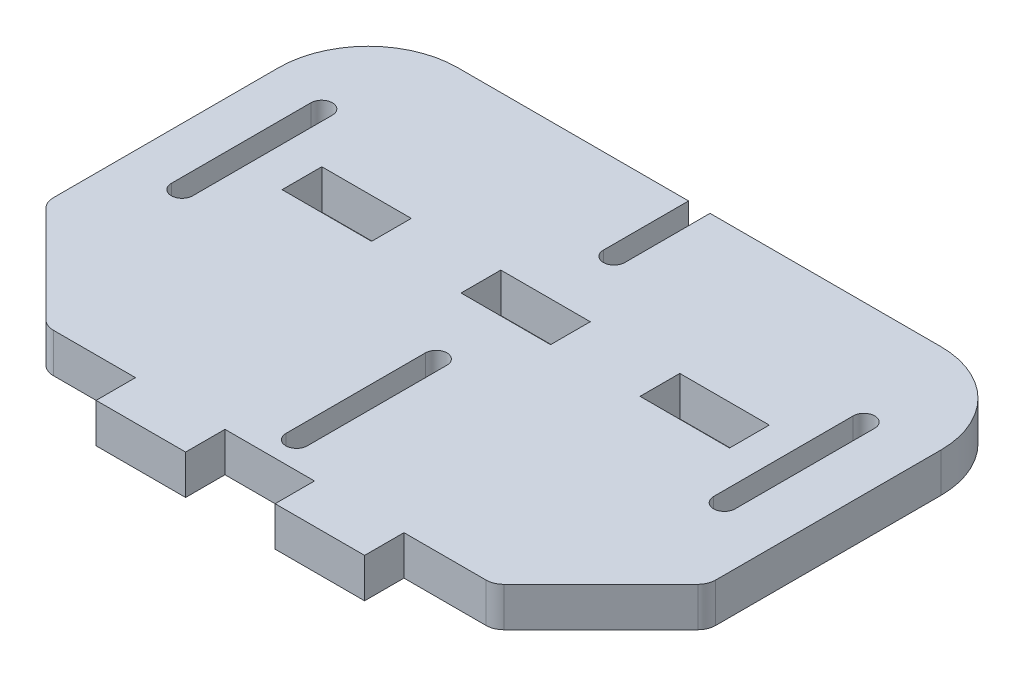
SolidWorks part; units mm, degrees
ref_plane "Front Plane" through (0, 0, 0) normal (0, 0, 1) x (1, 0, 0)
ref_plane "Top Plane" through (0, 0, 0) normal (0, 1, 0) x (1, 0, 0)
ref_plane "Right Plane" through (0, 0, 0) normal (1, 0, 0) x (0, 0, -1)
sketch "Sketch1" plane through (0, 0, 0) normal (0, 1, 0) x (1, 0, 0)
  line L8 (0, -7.5) -> (125, -7.5)
  line L12 (0, -7.5) -> (0, 3.5)
  line L14 (125, -7.5) -> (125, 3.5)
  line L17 (155, 33.5) -> (155, 123.5)
  line L18 (-30, 33.5) -> (-30, 123.5)
  line L23 (137.5, 55.5) -> (137.5, 94.5) construction
  line L24 (134.5, 55.5) -> (134.5, 94.5)
  line L25 (140.5, 55.5) -> (140.5, 94.5)
  line L26 (-14, 55.5) -> (-14, 94.5) construction
  line L27 (-17, 55.5) -> (-17, 94.5)
  line L28 (-11, 55.5) -> (-11, 94.5)
  line L29 (62.5, 11) -> (62.5, 50) construction
  line L30 (59.5, 11) -> (59.5, 50)
  line L31 (65.5, 11) -> (65.5, 50)
  line L32 (59.5, 123.5) -> (-30, 123.5)
  line L33 (65.5, 123.5) -> (65.5, 99.7057)
  line L34 (59.5, 123.5) -> (59.5, 99.7057)
  line L35 (155, 123.5) -> (65.5, 123.5)
  line L36 (125, 3.5) -> (155, 33.5)
  line L37 (0, 3.5) -> (-30, 33.5)
  arc A0 (134.5, 55.5) -> (140.5, 55.5) centre (137.5, 55.5) ccw
  arc A1 (140.5, 94.5) -> (134.5, 94.5) centre (137.5, 94.5) ccw
  arc A2 (-17, 55.5) -> (-11, 55.5) centre (-14, 55.5) ccw
  arc A3 (-11, 94.5) -> (-17, 94.5) centre (-14, 94.5) ccw
  arc A4 (59.5, 11) -> (65.5, 11) centre (62.5, 11) ccw
  arc A5 (65.5, 50) -> (59.5, 50) centre (62.5, 50) ccw
  arc A7 (59.5, 99.7057) -> (65.5, 99.7057) centre (62.5, 99.7057) ccw
  point P3 (-30, 36.5794)
  point P4 (-30, 36.317)
  point P5 (-30, 37.8917)
  point P6 (59.5, 123.4534)
  point P18 (137.5, 75)
  point P23 (-14, 75)
  point P30 (62.5, 30.5)
  dimension "D1" = 89.5
  dimension "D2" = 135
  dimension "D3" = 11
  dimension "D4" = 135
  dimension "D5" = 125
  dimension "D6" = 90
extrude "Boss-Extrude6" add sketch "Sketch1" along normal blind 11
sketch "Sketch4" plane through (0, 11, 0) normal (0, 1, 0) x (1, 0, 0)
  line L0 (0, -7.5) -> (125, -7.5) construction
  line L1 (0, -7.5) -> (25, -7.5)
  line L2 (0, -7.5) -> (0, 3.5)
  line L3 (0, 3.5) -> (25, 3.5)
  line L4 (25, -7.5) -> (25, 3.5)
  line L5 (50, -7.5) -> (75, -7.5)
  line L6 (50, -7.5) -> (50, 3.5)
  line L7 (50, 3.5) -> (75, 3.5)
  line L8 (75, -7.5) -> (75, 3.5)
  line L9 (0, 69.45) -> (25, 69.45)
  line L10 (125, -7.5) -> (100, -7.5)
  line L11 (125, -7.5) -> (125, 3.5)
  line L12 (125, 3.5) -> (100, 3.5)
  line L13 (100, -7.5) -> (100, 3.5)
  line L14 (0, 69.45) -> (0, 80.55)
  line L15 (0, 80.55) -> (25, 80.55)
  line L16 (25, 69.45) -> (25, 80.55)
  line L17 (50, 69.45) -> (75, 69.45)
  line L18 (50, 69.45) -> (50, 80.55)
  line L19 (50, 80.55) -> (75, 80.55)
  line L20 (75, 69.45) -> (75, 80.55)
  line L21 (125, 69.45) -> (100, 69.45)
  line L22 (125, 69.45) -> (125, 80.55)
  line L23 (125, 80.55) -> (100, 80.55)
  line L24 (100, 69.45) -> (100, 80.55)
  point P29 (50, 69.9955)
  point P30 (125, 75)
  dimension "D1" = 25
  dimension "D2" = 25
  dimension "D3" = 25
  dimension "D4" = 25
  dimension "D5" = 82.5
  dimension "D6" = 11.1
extrude "Cut-Extrude1" cut sketch "Sketch4" against normal through all
fillet "Fillet1" radius 25 2 edges at (155, 5.5, -123.5) (-30, 5.5, -123.5)
fillet "Fillet2" radius 5 4 edges at (155, 5.5, -33.5) (125, 5.5, -3.5) (0, 5.5, -3.5) (-30, 5.5, -33.5)
